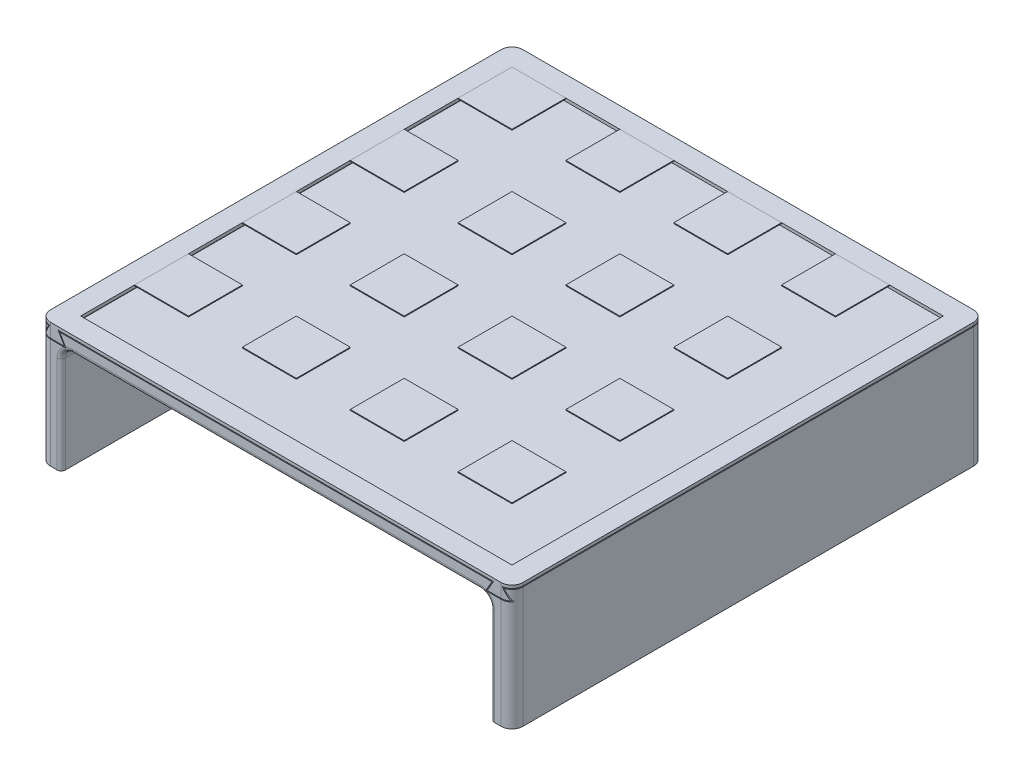
SolidWorks part; units mm, degrees
ref_plane "Front Plane" through (0, 0, 0) normal (0, 0, 1) x (1, 0, 0)
ref_plane "Top Plane" through (0, 0, 0) normal (0, 1, 0) x (1, 0, 0)
ref_plane "Right Plane" through (0, 0, 0) normal (1, 0, 0) x (0, 0, -1)
sketch "Sketch1" plane through (0, 0, 0) normal (0, 0, 1) x (1, 0, 0)
  line L0 (-99.5, -6) -> (99.5, -6)
  line L1 (-109.5, -56) -> (-99.5, -56)
  line L2 (-109.5, -56) -> (-109.5, 0)
  line L4 (-99.5, -56) -> (-99.5, -6)
  line L5 (0, -6) -> (0, 0) construction
  line L7 (-104.9204, 0.4) -> (-107.8072, -4.6)
  line L8 (-107.8072, -4.6) -> (-98.0337, -4.6)
  line L9 (-98.0337, -4.6) -> (-100.9204, 0.4)
  line L10 (-109.5, 0.4) -> (-104.9204, 0.4)
  line L14 (-100.9204, 0.4) -> (100.9204, 0.4)
  line L15 (0, 0.4) -> (0, 1.8) construction
  line L16 (109.5, 1.8) -> (-109.5, 1.8)
  line L17 (-109.5, 1.8) -> (-109.5, 0.4)
  line L18 (-105.6132, 0) -> (-108.5, -5)
  line L19 (-108.5, -5) -> (-97.3409, -5)
  line L20 (-97.3409, -5) -> (-100.2276, 0)
  line L21 (-109.5, 0) -> (-105.6132, 0)
  line L22 (-100.2276, 0) -> (100.2276, 0)
  line L23 (109.5, 1.4) -> (-109.5, 1.4) construction
  line L24 (109.5, 0) -> (105.6132, 0)
  line L25 (97.3409, -5) -> (100.2276, 0)
  line L26 (108.5, -5) -> (97.3409, -5)
  line L27 (105.6132, 0) -> (108.5, -5)
  line L28 (109.5, 1.8) -> (109.5, 0.4)
  line L29 (109.5, 0.4) -> (104.9204, 0.4)
  line L30 (98.0337, -4.6) -> (100.9204, 0.4)
  line L31 (107.8072, -4.6) -> (98.0337, -4.6)
  line L32 (104.9204, 0.4) -> (107.8072, -4.6)
  line L33 (99.5, -56) -> (99.5, -6)
  line L34 (109.5, -56) -> (109.5, 0)
  line L35 (109.5, -56) -> (99.5, -56)
  line L36 (-100.5, 0.4) -> (-100.5, 1.4) construction
  point P21 (0, 1.4)
  dimension "D1" = 109.5
  dimension "D2" = 4
  dimension "D5" = 0.4
  dimension "DovetailSpacing" = 0.4
  dimension "D6" = 0.4
  dimension "D7" = 0.4
  dimension "D8" = 5
  dimension "D3" = 60
  dimension "D4" = 60
  dimension "D9" = 0.4
  dimension "MetalSheetGap" = 1
  dimension "D10" = 1
  dimension "D11" = 10
  dimension "D12" = 1
  dimension "MainBoardSize" = 50
  dimension "D13" = 9
extrude "Boss-Extrude1" add sketch "Sketch1" along normal mid plane 219 contours L4 L0 L33 L35 L34 L24 L27 L26 L25 L22 L20 L19 L18 L21 L2 L1
extrude "Boss-Extrude2" add sketch "Sketch1<4>" along normal mid plane 219 separate body contours L16 L17 L10 L7 L8 L9 L14 L30 L31 L32 L29 L28
sketch "Sketch1<4>" plane through (0, 0, 0) normal (0, 0, 1) x (1, 0, 0) same geometry as "Sketch1"
sketch "Sketch2" plane through (0, 0.4, 0) normal (0, -1, 0) x (1, 0, 0)
  line L1 (-100, -100) -> (100, -100)
  line L2 (-100, -100) -> (-100, 100)
  line L3 (-100, 100) -> (100, 100)
  line L4 (100, -100) -> (100, 100)
  line L5 (-100, -100) -> (100, 100) construction
  line L6 (-100, 100) -> (100, -100) construction
  point P0 (0, 0)
  dimension "D1" = 200
  dimension "D2" = 200
extrude "Cut-Extrude1" cut sketch "Sketch2" against normal through all contours L3 L4 L1 L2
fillet "Fillet1" radius 5 2 edges at (99.5, -6, 0) (-99.5, -6, 0)
sketch "Sketch3" plane through (0, 0, 0) normal (0, 0, 1) x (1, 0, 0)
  line L1 (-99.5, -6) -> (99.5, -6)
  line L2 (-99.5, -6) -> (-99.5, -56)
  line L3 (-99.5, -56) -> (99.5, -56)
  line L4 (99.5, -6) -> (99.5, -56)
extrude "Boss-Extrude3" add sketch "Sketch3" along normal mid plane 10
fillet "Fillet2" radius 5 4 edges at (-109.5, -28, 109.5) (-109.5, -28, -109.5) (109.5, -28, -109.5) (109.5, -28, 109.5)
fillet "Fillet3" radius 5 4 edges at (-109.5, 1.1, -109.5) (109.5, 1.1, -109.5) (109.5, 1.1, 109.5) (-109.5, 1.1, 109.5)
fillet "Fillet4" radius 2 10 edges at (-99.5, -33.5, 109.5) (-98.0355, -7.4645, 109.5) (99.5, -33.5, 109.5) (98.0355, -7.4645, 109.5) (-99.5, -33.5, -109.5) (-98.0355, -7.4645, -109.5) (99.5, -33.5, -109.5) (98.0355, -7.4645, -109.5) (0, -6, 109.5) (0, -6, -109.5)
fillet "Fillet5" radius 1 10 edges at (-99.5, -33.5, -5) (-98.0355, -7.4645, -5) (0, -6, -5) (98.0355, -7.4645, -5) (-99.5, -33.5, 5) (-98.0355, -7.4645, 5) (0, -6, 5) (98.0355, -7.4645, 5) (99.5, -33.5, -5) (99.5, -33.5, 5)
sketch "Sketch4" plane through (0, 1.8, 0) normal (0, 1, 0) x (1, 0, 0)
  line L1 (-100, 100) -> (-75, 100)
  line L2 (-100, 100) -> (-100, 75)
  line L3 (-100, 75) -> (-75, 75)
  line L4 (-75, 100) -> (-75, 75)
  dimension "D1" = 25
  dimension "D2" = 25
extrude "Boss-Extrude4" add sketch "Sketch4" against normal blind 0.4 separate body
pattern_linear "LPattern1" count 4 spacing 50 along (1, 0, 0) count 4 spacing 50 along (0, 0, 1) of "Boss-Extrude4"
sketch "Sketch5" plane through (0, 1.8, 0) normal (0, 1, 0) x (1, 0, 0)
  line L1 (-75, 75) -> (-50, 75)
  line L2 (-75, 75) -> (-75, 50)
  line L3 (-75, 50) -> (-50, 50)
  line L4 (-50, 75) -> (-50, 50)
equation "\"D6@Sketch1\"=\"DovetailSpacing@Sketch1\""
equation "\"D7@Sketch1\"=\"DovetailSpacing@Sketch1\""
equation "\"D4@Sketch1\"=\"D3@Sketch1\""
equation "\"CheckerPatternThickness\"= 0.2mm * 2'How thick the squares the pecies sit on should be"
equation "\"D9@Sketch1\"=\"CheckerPatternThickness\""
equation "\"D2@Sketch2\"=\"D1@Sketch2\""
